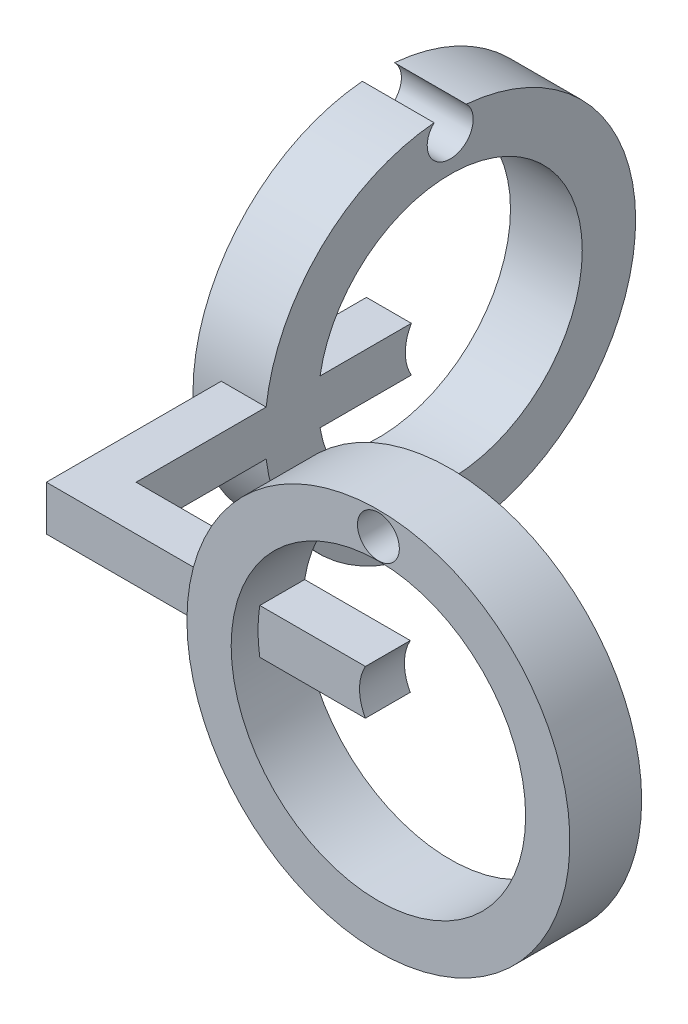
SolidWorks part; units mm, degrees
ref_plane "Front Plane" through (0, 0, 0) normal (0, 0, 1) x (1, 0, 0)
ref_plane "Top Plane" through (0, 0, 0) normal (0, 1, 0) x (1, 0, 0)
ref_plane "Right Plane" through (0, 0, 0) normal (1, 0, 0) x (0, 0, -1)
sketch "Sketch1" plane through (0, 0, 0) normal (0, 1, 0) x (1, 0, 0)
  line L0 (0, 0) -> (0, 70)
  line L1 (0, 70) -> (-10, 70)
  line L2 (-10, 70) -> (-10, -10)
  line L3 (-10, -10) -> (70, -10)
  line L4 (70, -10) -> (70, 0)
  line L5 (70, 0) -> (0, 0)
  dimension "D1" = 10
  dimension "D2" = 10
  dimension "D3" = 70
  dimension "D4" = 70
extrude "Boss-Extrude1" add sketch "Sketch1" along normal blind 10
sketch "Sketch3" plane through (0, 0, 10) normal (0, 0, 1) x (1, 0, 0)
  line L0 (70, 10) -> (70, 0) construction
  circle A0 centre (65, 5) radius 5
  point P2 (0, 0)
  point P5 (70, 5)
  point P6 (45.1207, 5)
  dimension "D1" = 10
  dimension "D2" = 5
extrude "Boss-Extrude2" add sketch "Sketch3" along normal blind 5
sketch "Sketch4" plane through (0, 0, 15) normal (0, 0, 1) x (1, 0, 0)
  line L0 (70, 10) -> (70, 0) construction
  line L1 (68.2727, 5.5) -> (55.4303, 5.5)
  line L2 (68.2727, 5.5) -> (68.2727, 4.5)
  line L3 (68.2727, 4.5) -> (55.4303, 4.5)
  line L4 (55.4303, 5.5) -> (55.4303, 4.5)
  point P6 (70, 5)
  point P7 (55.4303, 5)
  point P8 (55.4303, 4.5)
  dimension "D1" = 1
  dimension "D2" = 12.8424
extrude "Cut-Extrude1" cut sketch "Sketch4" against normal blind 5
sketch "Sketch5" plane through (-10, 0, 0) normal (-1, 0, 0) x (0, 0, 1)
  line L0 (-70, 10) -> (-70, 0) construction
  circle A0 centre (-44.3546, 5) radius 3.4181
  point P2 (0, 0)
  point P5 (-70, 5)
extrude "Boss-Extrude3" add sketch "Sketch5" along normal blind 5
sketch "Sketch6" plane through (-15, 0, 0) normal (-1, 0, 0) x (0, 0, 1)
  line L0 (10, 0) -> (10, 5) construction
  line L1 (-54.6363, 3) -> (-45.2893, 3)
  line L2 (-54.6363, 3) -> (-54.6363, 2)
  line L3 (-54.6363, 2) -> (-45.2893, 2)
  line L4 (-45.2893, 3) -> (-45.2893, 2)
  point P4 (-45.2893, 2.5)
  point P7 (10, 2.5)
  dimension "D1" = 1
  dimension "D2" = 9.347
extrude "Cut-Extrude2" cut sketch "Sketch6" against normal blind 5
sketch "Sketch7" plane through (0, 0, 0) normal (0, 0, -1) x (-1, 0, 0)
  line L0 (-70, 10) -> (-70, 0) construction
  circle A0 centre (-70, 5) radius 42.6681
  circle A1 centre (-70, 5) radius 32.8121
  point P3 (0, 0)
  point P5 (-70, 5)
extrude "Boss-Extrude4" add sketch "Sketch7" against normal blind 16
sketch "Sketch8" plane through (0, 0, 0) normal (0, 0, -1) x (-1, 0, 0)
  circle A0 centre (-70, 5) radius 10.2043
extrude "Cut-Extrude3" cut sketch "Sketch8" against normal blind 16
sketch "Sketch9" plane through (0, 0, 0) normal (1, 0, 0) x (0, 0, -1)
  line L0 (70, 10) -> (70, 0) construction
  circle A0 centre (70, 5) radius 41.3208
  circle A1 centre (70, 5) radius 29.4318
  point P3 (0, 0)
  point P6 (70, 5)
  point P7 (0, 0)
extrude "Boss-Extrude5" add sketch "Sketch9" against normal blind 16
sketch "Sketch10" plane through (0, 0, 0) normal (1, 0, 0) x (0, 0, -1)
  circle A0 centre (70, 5) radius 10.0021
extrude "Cut-Extrude4" cut sketch "Sketch10" against normal blind 16
sketch "Sketch11" plane through (0, 0, 0) normal (1, 0, 0) x (0, 0, -1)
  circle A0 centre (70, 5) radius 37.5
  circle A1 centre (70, 42.5) radius 5.1255
  arc M2 (28.9828, 0) -> (28.9828, 10) centre (70, 5) ccw
  dimension "D1" = 75
extrude "Cut-Extrude5" cut sketch "Sketch11" against normal blind 16 contours A1 A0 M2 | A0 A1 region at (0, 40.2628, -70) region at (0, 44.2151, -70)
sketch "Sketch12" plane through (0, 0, 0) normal (0, 0, -1) x (-1, 0, 0)
  circle A0 centre (-70, 5) radius 37.5
  circle A1 centre (-70, 42.5) radius 4.6621
  dimension "D1" = 75
extrude "Cut-Extrude6" cut sketch "Sketch12" against normal blind 16 contours A0 A1 | A0 A1 region at (70, 40.4701, 0) region at (70, 44.4255, 0)
